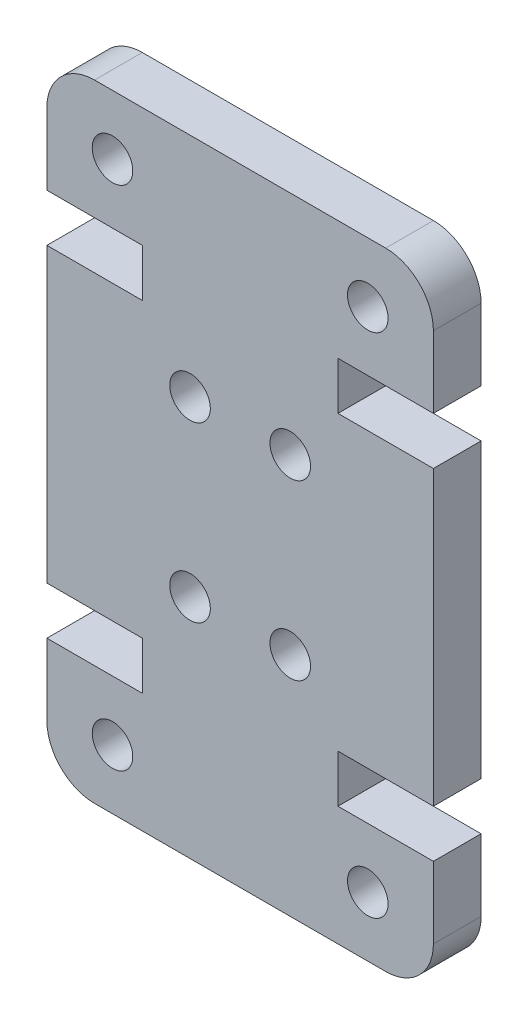
SolidWorks part; units mm, degrees
ref_plane "Front Plane" through (0, 0, 0) normal (0, 0, 1) x (1, 0, 0)
ref_plane "Top Plane" through (0, 0, 0) normal (0, 1, 0) x (1, 0, 0)
ref_plane "Right Plane" through (0, 0, 0) normal (1, 0, 0) x (0, 0, -1)
sketch "Sketch2" plane through (0, 0, 0) normal (0, 0, 1) x (1, 0, 0)
  line L0 (0, 13.13) -> (16.2, 13.13) construction
  line L1 (8.1, 26.26) -> (8.1, 0) construction
  line L2 (0, 7) -> (0, 19.26)
  line L3 (2, 0) -> (14.2, 0)
  line L4 (16.2, 2) -> (16.2, 5)
  line L5 (12.2, 5) -> (16.2, 5)
  line L6 (16.2, 7) -> (12.2, 7)
  line L7 (12.2, 7) -> (12.2, 5)
  line L8 (16.2, 7) -> (16.2, 19.26)
  line L9 (0, 24.26) -> (0, 21.26)
  line L10 (4, 21.26) -> (0, 21.26)
  line L11 (0, 19.26) -> (4, 19.26)
  line L12 (4, 19.26) -> (4, 21.26)
  line L13 (12.2, 19.26) -> (12.2, 21.26)
  line L14 (16.2, 19.26) -> (12.2, 19.26)
  line L15 (12.2, 21.26) -> (16.2, 21.26)
  line L16 (16.2, 24.26) -> (16.2, 21.26)
  line L17 (2, 26.26) -> (14.2, 26.26)
  line L27 (4, 7) -> (4, 5)
  line L30 (0, 7) -> (4, 7)
  line L32 (4, 5) -> (0, 5)
  line L36 (0, 2) -> (0, 5)
  circle A0 centre (13.45, 2.5) radius 0.85
  circle A1 centre (10.2, 9.5) radius 0.85
  arc A2 (16.2, 2) -> (14.2, 0) centre (14.2, 2) cw
  circle A3 centre (2.75, 23.76) radius 0.85
  circle A4 centre (6, 16.76) radius 0.85
  arc A5 (0, 24.26) -> (2, 26.26) centre (2, 24.26) cw
  arc A6 (16.2, 24.26) -> (14.2, 26.26) centre (14.2, 24.26) ccw
  circle A7 centre (10.2, 16.76) radius 0.85
  circle A8 centre (13.45, 23.76) radius 0.85
  arc A17 (0, 2) -> (2, 0) centre (2, 2) ccw
  circle A19 centre (6, 9.5) radius 0.85
  circle A21 centre (2.75, 2.5) radius 0.85
  point P16 (8.1, 13.13)
  dimension "D1" = 1.7
  dimension "D2" = 2
  dimension "D3" = 2.75
  dimension "D4" = 6
  dimension "D5" = 8.1
  dimension "D6" = 2.5
  dimension "D9" = 9.5
  dimension "D10" = 13.13
  dimension "D7" = 5
extrude "Boss-Extrude1" add sketch "Sketch2" along normal blind 4
sketch "Sketch3" plane through (0, 0, 4) normal (0, 0, 1) x (1, 0, 0)
  line L0 (0, 0) -> (0, 26.26)
  line L1 (0, 26.26) -> (16.2, 26.26)
  line L2 (16.2, 26.26) -> (16.2, 0)
  line L3 (16.2, 0) -> (0, 0)
extrude "Cut-Extrude1" cut sketch "Sketch3" against normal blind 2
equation "\"D5@Sketch2\"= \"fingerWidth@parametersSketch@prostheticParameters.SLDPRT\" / 2'Finger Width"
equation "\"D10@Sketch2\"= ( ( \"HL@parametersSketch@prostheticParameters.SLDPRT\" * 0.196 ) - 4 - 6 ) / 2 'PIP Length"
equation "\"D1@Sketch2\"= 1.5 + \"tol1@parametersSketch@prostheticParameters.SLDPRT\""
